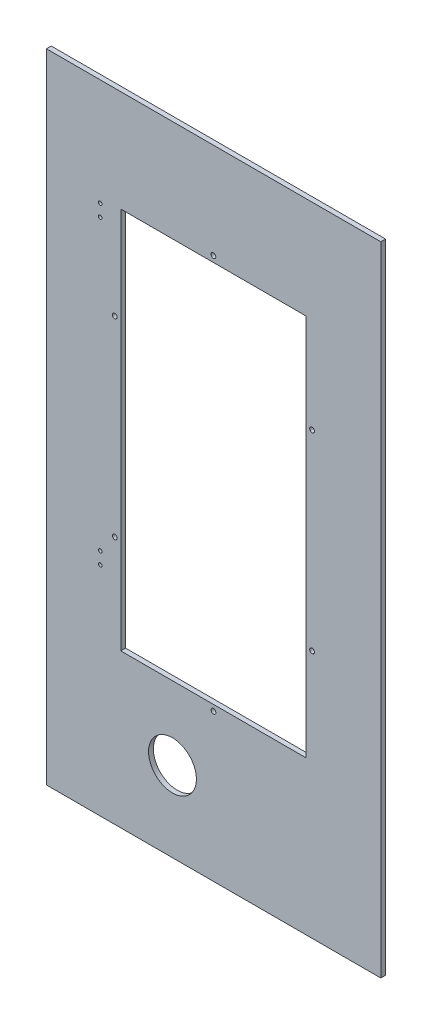
SolidWorks part; units mm, degrees
ref_plane "Спереди" through (0, 0, 0) normal (0, 0, 1) x (1, 0, 0)
ref_plane "Сверху" through (0, 0, 0) normal (0, 1, 0) x (1, 0, 0)
ref_plane "Справа" through (0, 0, 0) normal (1, 0, 0) x (0, 0, -1)
sketch "Эскиз1" plane through (0, 0, 0) normal (0, 1, 0) x (1, 0, 0)
  line L1 (-144.7882, -2.3414) -> (134.7883, -2.3414)
  line L2 (-144.7882, -2.3414) -> (-144.7882, -6.3414)
  line L3 (-144.7882, -6.3414) -> (134.7883, -6.3414)
  line L4 (134.7883, -2.3414) -> (134.7883, -6.3414)
extrude "Вытянуть1" add sketch "Эскиз1" along normal up to surface (533.2137 mm away)
sketch "Эскиз2" plane through (0, 0, 2.3414) normal (0, 0, -1) x (-1, 0, 0)
  circle A0 centre (39.3967, 66.9121) radius 20
extrude "Вырез-Вытянуть1" cut sketch "Эскиз2" against normal through all
sketch "Эскиз3" plane through (0, 0, 6.3414) normal (0, 0, 1) x (1, 0, 0)
  line L1 (-82.6488, 448.2137) -> (72.3512, 448.2137)
  line L2 (-82.6488, 448.2137) -> (-82.6488, 128.2137)
  line L3 (-82.6488, 128.2137) -> (72.3512, 128.2137)
  line L4 (72.3512, 448.2137) -> (72.3512, 128.2137)
extrude "Cut-Extrude1" cut sketch "Эскиз3" against normal through all
sketch "Sketch1" plane through (0, 0, 6.3414) normal (0, 0, 1) x (1, 0, 0)
  line L0 (72.3512, 448.2137) -> (-82.6488, 448.2137) construction
  line L1 (-82.6488, 448.2137) -> (-82.6488, 128.2137) construction
  line L2 (-5.1488, 447.7153) -> (-5.1488, 464.7544) construction
  line L3 (72.3512, 288.2137) -> (113.04, 288.2137) construction
  circle A0 centre (-87.6488, 368.2137) radius 2
  circle A1 centre (-87.6488, 208.2137) radius 2
  circle A2 centre (77.3512, 208.2137) radius 2
  circle A3 centre (77.3512, 368.2137) radius 2
  circle A4 centre (-5.1488, 453.2137) radius 2
  circle A5 centre (-5.1488, 123.2137) radius 2
  circle A6 centre (-99.818, 443.8535) radius 1.5
  circle A7 centre (-99.818, 433.681) radius 1.5
  circle A8 centre (-99.818, 192.0819) radius 1.5
  circle A9 centre (-99.818, 181.9094) radius 1.5
  dimension "D1" = 80
  dimension "D3" = 5
  dimension "D2" = 5
extrude "Cut-Extrude2" cut sketch "Sketch1" against normal through all
